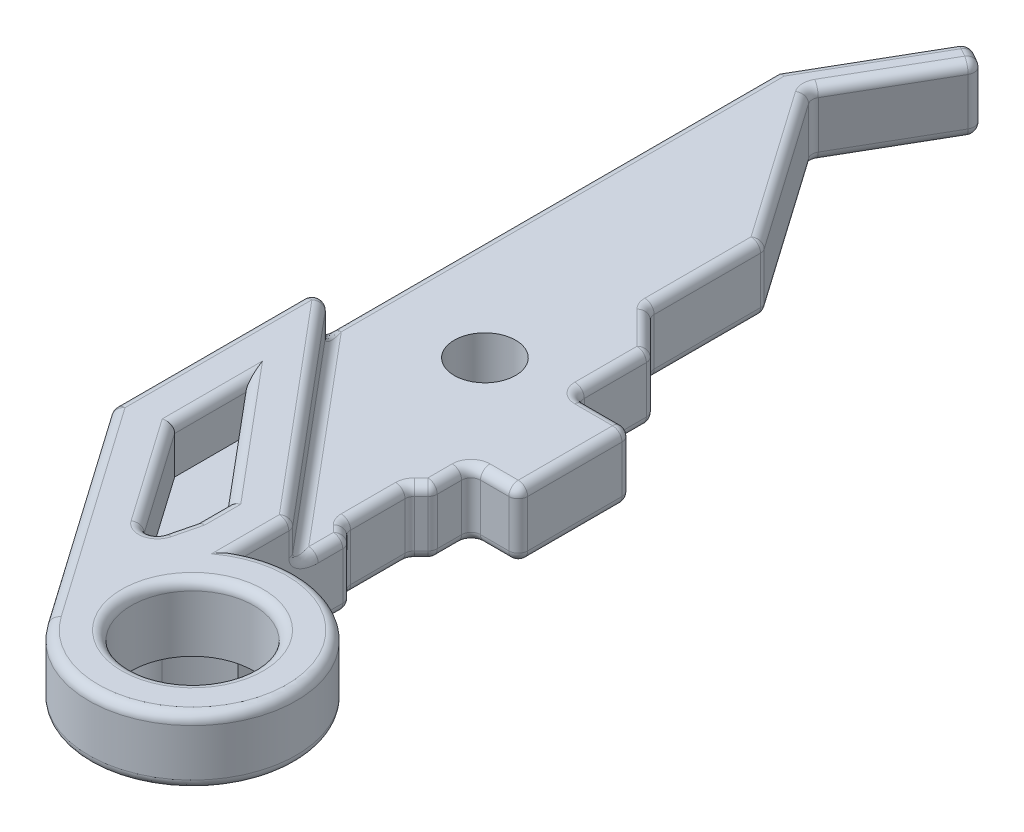
SolidWorks part; units mm, degrees
ref_plane "Front Plane" through (0, 0, 0) normal (0, 0, 1) x (1, 0, 0)
ref_plane "Top Plane" through (0, 0, 0) normal (0, 1, 0) x (1, 0, 0)
ref_plane "Right Plane" through (0, 0, 0) normal (1, 0, 0) x (0, 0, -1)
sketch "Sketch1" plane through (0, 0, 0) normal (0, 1, 0) x (1, 0, 0)
  line L1 (25, -50) -> (-25, -50)
  line L2 (25, -50) -> (25, 50)
  line L3 (25, 50) -> (-25, 50)
  line L4 (-25, -50) -> (-25, 50)
  line L5 (25, -50) -> (-25, 50) construction
  line L6 (25, 50) -> (-25, -50) construction
  point P0 (0, 0)
  dimension "D1" = 100
  dimension "D2" = 50
sketch "Sketch2" plane through (0, 0, 0) normal (0, 1, 0) x (1, 0, 0)
  line L0 (25, -50) -> (-25, -50) construction
  line L1 (-9.0107, -56.3093) -> (-25, -33.4742)
  line L2 (-25, -50) -> (-25, 50) construction
  line L3 (-25, -33.4742) -> (-25, 37.0096)
  line L4 (-25, 37.0096) -> (-17.5, 50)
  line L5 (25, 50) -> (-25, 50) construction
  line L6 (0, -39) -> (0, 50) construction
  line L7 (-17.5, 50) -> (-14.9019, 48.5)
  line L8 (-14.9019, 48.5) -> (-21.5359, 37.0096)
  line L9 (-21.5359, 37.0096) -> (-10, 20.5346)
  line L10 (-10, 20.5346) -> (-10, 8.5346)
  line L11 (-10, 8.5346) -> (-6, 4.5346)
  line L12 (-6, 4.5346) -> (-6, -3.4654)
  line L13 (-6, -3.4654) -> (0, -3.4654)
  line L14 (0, -3.4654) -> (0, -15.4654)
  line L15 (0, -15.4654) -> (-5, -15.4654)
  line L16 (-5, -15.4654) -> (-5, -19.4654)
  line L17 (-5, -19.4654) -> (-6.2952, -20.7605)
  line L18 (-6.2952, -20.7605) -> (-6.2952, -27.3602)
  line L19 (-6.2952, -27.3602) -> (-5, -28.6554)
  line L20 (-5, -28.6554) -> (-5, -40.202)
  circle A0 centre (0, -50) radius 11
  circle A1 centre (0, -50) radius 6.5
  circle A2 centre (0, 37.9499) radius 18.1805 construction
  circle A3 centre (0, 12.6768) radius 10 construction
  dimension "D1" = 22
  dimension "D2" = 13
  dimension "D7" = 8
  dimension "D10" = 20
  dimension "D3" = 15
  dimension "D4" = 3
  dimension "D5" = 115
  dimension "D6" = 30
  dimension "D8" = 45
  dimension "D9" = 12
  dimension "D11" = 12
  dimension "D12" = 12
  dimension "D13" = 4
  dimension "D14" = 45
  dimension "D15" = 6.5997
  dimension "D16" = 5
  dimension "D17" = 35
extrude "Boss-Extrude1" add sketch "Sketch2" along normal mid plane 7 contours A0 L19 L18 L17 L16 L15 L14 L13 L12 L11 L10 L9 L8 L7 L4 L3 L1 region at (-15.4236, 0, 7.0756)
extrude "Boss-Extrude3" add sketch "Sketch2<3>" along normal blind 7 from offset 1 contours A0 A1 region at (-10.3722, 0, 47.4174)
sketch "Sketch2<3>" plane through (0, 0, 0) normal (0, 1, 0) x (1, 0, 0) same geometry as "Sketch2"
sketch "Sketch4" plane through (0, 0, 0) normal (0, 1, 0) x (1, 0, 0)
  line L0 (-25, -33.4742) -> (-25, -10.5936)
  line L1 (-25, -50) -> (-25, 50) construction
  line L2 (-25, -10.5936) -> (-5, -34.4287)
  line L4 (-25, -33.4742) -> (-9.0107, -56.3093)
  line L5 (-9.0107, -56.3093) -> (-25, -33.4742) construction
  line L6 (25, -50) -> (-25, -50) construction
  line L7 (-5, -34.4287) -> (-5, -40.202)
  line L8 (-5, -28.6554) -> (-5, -40.202) construction
  line L9 (-9.0107, -56.3093) -> (-25, -33.4742) construction
  arc A0 (-5, -40.202) -> (-9.0107, -56.3093) centre (0, -50) ccw
  dimension "D1" = 40
extrude "Boss-Extrude2" add sketch "Sketch4" along normal mid plane 16
sketch "Sketch5" plane through (0, 8, 0) normal (0, 1, 0) x (1, 0, 0)
  line L0 (-10, -39.5889) -> (-11.2105, -44.4504) construction
  line L1 (-11.2105, -44.4504) -> (-20, -31.8977) construction
  line L36 (-5, -40.202) -> (-9.0107, -56.3093) construction
  line L37 (-9.0107, -56.3093) -> (-25, -33.4742) construction
  line L38 (-25, -33.4742) -> (-25, -10.5936) construction
  line L39 (-25, -10.5936) -> (-5, -34.4287) construction
  line L40 (-5, -34.4287) -> (-5, -40.202) construction
  line L41 (-10, -36.2486) -> (-10, -39.5889)
  line L42 (-10, -39.5889) -> (-10.6801, -42.3203)
  line L43 (-12.4696, -42.6522) -> (-20, -31.8977)
  line L44 (-20, -31.8977) -> (-20, -24.331)
  line L45 (-20, -24.331) -> (-10, -36.2486)
  arc A0 (-10.6801, -42.3203) -> (-12.4696, -42.6522) centre (-11.6505, -42.0786) cw
  dimension "D2" = 1
  dimension "D1" = 5
extrude "Cut-Extrude1" cut sketch "Sketch5" against normal blind 5
mirror "Mirror1" about plane through (0, 0, 0) normal (0, 1, 0) of "Cut-Extrude1"
fillet "Fillet1" radius 5 2 edges at (-9.0107, -3.5, 56.3093) (-9.0107, 4.5, 56.3093)
fillet "Fillet2" radius 1 14 edges at (-5, 0, 28.6554) (-6.2952, 0, 27.3602) (-6.2952, 0, 20.7605) (-5, 0, 19.4654) (-5, 0, 15.4654) (0, 0, 15.4654) (0, 0, 3.4654) (-6, 0, 3.4654) (-6, 0, -4.5346) (-10, 0, -8.5346) (-10, 0, -20.5346) (-21.5359, 0, -37.0096) (-17.5, 0, -50) (-14.9019, 0, -48.5)
fillet "Fillet3" radius 1 93 edges at (-25, -5.75, 10.5936) (-5, -5.75, 34.4287) (-25, 5.75, 10.5936) (-5, 5.75, 34.4287) (10.6741, 1, 52.6578) (-25, 0, 33.4742) (-13.2644, 1, 50.2343) (-17.0053, 8, 44.8918) (-25, 8, 22.0339) (-15, 8, 22.5112) (-5, 8, 37.3154) (10.6741, 8, 52.6578) (0, 8, 56.5) (-20, 8, 28.1144) (-16.2348, 8, 37.275) (-10.34, 8, 40.9546) (-10, 8, 37.9187) (-15, 8, 30.2898) (-5, -8, 37.3154) (-15, -8, 22.5112) (-25, -8, 22.0339) (-21.2591, -8, 38.8168) (-13.3341, -8, 46.2907) (-7.3647, -8, 41.8293) (-6.2191, -3.5, 27.3287) (-6.2952, -3.5, 24.0604) (-6.2191, -3.5, 20.7921) (-5.6476, -3.5, 20.1129) (-5.0761, -3.5, 19.4338) (-5, -3.5, 17.7582) (-4.7071, -3.5, 15.7582) (-2.5, -3.5, 15.4654) (-0.2929, -3.5, 15.1725) (0, -3.5, 9.4654) (-0.2929, -3.5, 3.7582) (-3, -3.5, 3.4654) (-5.7071, -3.5, 3.1725) (-6, -3.5, -0.8275) (-6.0761, -3.5, -4.5031) (-8, -3.5, -6.5346) (-9.9239, -3.5, -8.5662) (-10, -3.5, -14.5841) (-10.0463, -3.5, -20.5201) (-15.6757, -3.5, -28.6403) (-21.3504, -3.5, -37.0177) (-18.3096, -3.5, -42.5977) (-15.302, -3.5, -48.3928) (-16.201, -3.5, -49.25) (-17.3928, -3.5, -49.5999) (-21.5, -3.5, -43.0718) (-25, -3.5, -13.208) (-15, -3.5, 22.5112) (-5, -3.5, 31.7491) (-5.0761, -3.5, 28.6869) (-5.6476, -3.5, 28.0078) (-15, 3.5, 22.5112) (-25, 3.5, -13.208) (-21.5, 3.5, -43.0718) (-17.3928, 3.5, -49.5999) (-16.201, 3.5, -49.25) (-15.302, 3.5, -48.3928) (-18.3096, 3.5, -42.5977) (-21.3504, 3.5, -37.0177) (-15.6757, 3.5, -28.6403) (-10.0463, 3.5, -20.5201) (-10, 3.5, -14.5841) (-9.9239, 3.5, -8.5662) (-8, 3.5, -6.5346) (-6.0761, 3.5, -4.5031) (-6, 3.5, -0.8275) (-5.7071, 3.5, 3.1725) (-3, 3.5, 3.4654) (-0.2929, 3.5, 3.7582) (0, 3.5, 9.4654) (-0.2929, 3.5, 15.1725) (-2.5, 3.5, 15.4654) (-4.7071, 3.5, 15.7582) (-5, 3.5, 17.7582) (-5.0761, 3.5, 19.4338) (-5.6476, 3.5, 20.1129) (-6.2191, 3.5, 20.7921) (-6.2952, 3.5, 24.0604) (-6.2191, 3.5, 27.3287) (-5.6476, 3.5, 28.0078) (-5.0761, 3.5, 28.6869) (-5, 3.5, 31.7491) (-10, -8, 37.9187) (-10.34, -8, 40.9546) (-16.2348, -8, 37.275) (-20, -8, 28.1144) (-15, -8, 30.2898) (-11.4681, 8, 43.0619) (-11.4681, -8, 43.0619)
sketch "Sketch6" plane through (0, 3.5, 0) normal (0, 1, 0) x (1, 0, 0)
  line L0 (0, 0) -> (0, -30) construction
  line L1 (-14, -5) -> (0, -5) construction
  line L2 (0, -50) -> (0, -30) construction
  line L3 (-14, -5) -> (0, -30) construction
  circle A0 centre (-14, -5) radius 3.25
  circle A1 centre (0, -50) radius 6.5 construction
  circle A2 centre (0, -30) radius 5 construction
  dimension "D1" = 6.5
  dimension "D2" = 28
  dimension "D3" = 45
  dimension "D4" = 10
  dimension "D5" = 20
extrude "Cut-Extrude2" cut sketch "Sketch6" against normal through all
